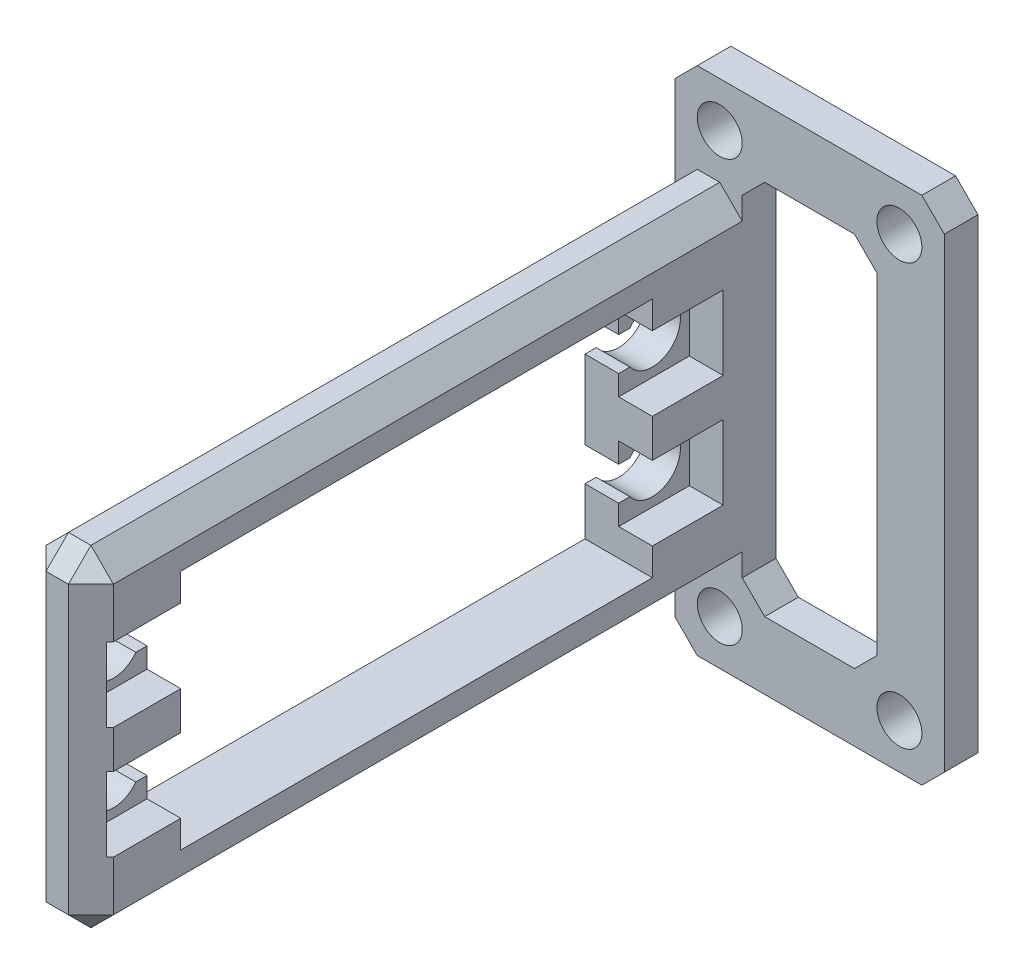
SolidWorks part; units mm, degrees
ref_plane "Front Plane" through (0, 0, 0) normal (0, 0, 1) x (1, 0, 0)
ref_plane "Top Plane" through (0, 0, 0) normal (0, 1, 0) x (1, 0, 0)
ref_plane "Right Plane" through (0, 0, 0) normal (1, 0, 0) x (0, 0, -1)
sketch "Sketch1" plane through (0, 0, 0) normal (1, 0, 0) x (0, 0, -1)
  line L0 (-38.5085, 0.4505) -> (19.4915, 0.4505) construction
  line L1 (-38.5085, 15.2005) -> (19.4915, 15.2005)
  line L2 (-31.5085, 6.9505) -> (-30.5085, 6.9505)
  line L3 (-38.5085, 15.2005) -> (-38.5085, -14.2995)
  line L4 (-38.5085, -14.2995) -> (19.4915, -14.2995)
  line L5 (-30.5085, 3.9505) -> (-31.5085, 3.9505)
  line L6 (11.4915, 3.9505) -> (12.4915, 3.9505)
  line L7 (19.4915, 15.2005) -> (19.4915, -14.2995)
  line L8 (12.4915, 6.9505) -> (11.4915, 6.9505)
  line L9 (11.4915, -3.0495) -> (12.4915, -3.0495)
  line L10 (12.4915, -6.0495) -> (11.4915, -6.0495)
  line L11 (-30.5085, -3.0495) -> (-31.5085, -3.0495)
  line L12 (-28.5085, 10.2005) -> (9.4915, 10.2005) construction
  line L13 (11.4915, -10.2995) -> (-30.5085, -10.2995)
  line L14 (11.4915, 11.2005) -> (-30.5085, 11.2005)
  line L15 (-31.5085, -6.0495) -> (-30.5085, -6.0495)
  line L16 (-30.5085, 3.9505) -> (-30.5085, -3.0495)
  line L17 (-30.5085, -6.0495) -> (-30.5085, -10.2995)
  line L18 (11.4915, -6.0495) -> (11.4915, -10.2995)
  line L19 (11.4915, 3.9505) -> (11.4915, -3.0495)
  line L27 (11.4915, 11.2005) -> (11.4915, 6.9505)
  line L28 (-30.5085, 11.2005) -> (-30.5085, 6.9505)
  line L30 (9.4915, -9.2995) -> (-28.5085, -9.2995) construction
  line L32 (-29.5085, 9.2005) -> (-29.5085, -8.2995) construction
  line L35 (-9.5085, 11.2005) -> (-9.5085, -10.2995) construction
  arc A0 (-31.5085, 6.9505) -> (-31.5085, 3.9505) centre (-33.5085, 5.4505) ccw
  arc A1 (-31.5085, -3.0495) -> (-31.5085, -6.0495) centre (-33.5085, -4.5495) ccw
  arc A2 (12.4915, 3.9505) -> (12.4915, 6.9505) centre (14.4915, 5.4505) ccw
  arc A3 (12.4915, -6.0495) -> (12.4915, -3.0495) centre (14.4915, -4.5495) ccw
  arc A4 (16.3914, 7.0755) -> (16.3914, 3.8255) centre (14.4915, 5.4505) ccw construction
  arc A5 (16.3914, -2.9245) -> (16.3914, -6.1745) centre (14.4915, -4.5495) ccw construction
  arc A6 (-35.4083, -6.1745) -> (-35.4083, -2.9245) centre (-33.5085, -4.5495) ccw construction
  arc A7 (-35.4083, 3.8255) -> (-35.4083, 7.0755) centre (-33.5085, 5.4505) ccw construction
  dimension "D3" = 3
  dimension "D1" = 1
  dimension "D2" = 4
  dimension "D4" = 1
  dimension "D5" = 1
  dimension "D6" = 8
extrude "Boss-Extrude1" add sketch "Sketch1" along normal blind 6
sketch "Sketch2" plane through (6, 0, 0) normal (1, 0, 0) x (0, 0, -1)
  line L0 (-9.5085, 11.2005) -> (-9.5085, -10.2995) construction
  line L1 (-36.8085, 2.1505) -> (-30.2085, 2.1505)
  line L2 (-36.8085, 2.1505) -> (-36.8085, 8.7505)
  line L3 (-36.8085, 8.7505) -> (-30.2085, 8.7505)
  line L4 (-30.2085, 2.1505) -> (-30.2085, 8.7505)
  line L5 (-36.8085, 2.1505) -> (-30.2085, 8.7505) construction
  line L6 (-36.8085, 8.7505) -> (-30.2085, 2.1505) construction
  line L7 (11.4915, 11.2005) -> (-30.5085, 11.2005) construction
  line L8 (11.4915, -10.2995) -> (-30.5085, -10.2995) construction
  line L9 (-38.5085, 0.4505) -> (19.4915, 0.4505) construction
  line L12 (17.7915, 8.7505) -> (11.1915, 2.1505) construction
  line L13 (17.7915, 2.1505) -> (11.1915, 8.7505) construction
  line L14 (11.1915, 2.1505) -> (11.1915, 8.7505)
  line L15 (17.7915, 8.7505) -> (11.1915, 8.7505)
  line L16 (17.7915, 2.1505) -> (17.7915, 8.7505)
  line L17 (17.7915, 2.1505) -> (11.1915, 2.1505)
  line L18 (-38.5085, 15.2005) -> (-38.5085, -14.2995) construction
  line L19 (19.4915, 15.2005) -> (19.4915, -14.2995) construction
  line L20 (-36.8085, -7.8495) -> (-30.2085, -1.2495) construction
  line L21 (-36.8085, -1.2495) -> (-30.2085, -7.8495) construction
  line L22 (-30.2085, -1.2495) -> (-30.2085, -7.8495)
  line L23 (-36.8085, -7.8495) -> (-30.2085, -7.8495)
  line L24 (-36.8085, -1.2495) -> (-36.8085, -7.8495)
  line L25 (-36.8085, -1.2495) -> (-30.2085, -1.2495)
  line L26 (17.7915, -1.2495) -> (11.1915, -7.8495) construction
  line L27 (17.7915, -7.8495) -> (11.1915, -1.2495) construction
  line L28 (17.7915, -1.2495) -> (11.1915, -1.2495)
  line L29 (17.7915, -1.2495) -> (17.7915, -7.8495)
  line L30 (17.7915, -7.8495) -> (11.1915, -7.8495)
  line L31 (11.1915, -1.2495) -> (11.1915, -7.8495)
  point P0 (-33.5085, 5.4505)
  point P1 (-33.5085, 5.4505)
  point P23 (14.4915, 5.4505)
  point P28 (-33.5085, -4.5495)
  point P33 (14.4915, -4.5495)
  dimension "D1" = 6.6
extrude "Cut-Extrude1" cut sketch "Sketch2" against normal blind 3
sketch "Sketch3" plane through (0, 0, -19.4915) normal (0, 0, -1) x (-1, 0, 0)
  line L0 (0, -22.2995) -> (0, 23.2005)
  line L1 (0, 23.2005) -> (-24, 23.2005)
  line L2 (-24, 23.2005) -> (-24, -22.2995)
  line L3 (-24, 0.4505) -> (0, 0.4505) construction
  line L4 (0, 15.2005) -> (0, -14.2995) construction
  line L5 (-4, 19.2005) -> (-4, 23.2005) construction
  line L6 (-4, 19.2005) -> (0, 19.2005) construction
  line L7 (-12, 23.2005) -> (-12, -22.2995) construction
  line L8 (-4, -18.2995) -> (0, -18.2995) construction
  line L9 (-4, -18.2995) -> (-4, -22.2995) construction
  line L10 (0, -22.2995) -> (-24, -22.2995)
  line L12 (-6, -16.2995) -> (-18, -16.2995)
  line L13 (-6, -16.2995) -> (-6, 17.2005)
  line L14 (-6, 17.2005) -> (-18, 17.2005)
  line L15 (-18, -16.2995) -> (-18, 17.2005)
  line L16 (-6, -16.2995) -> (-18, 17.2005) construction
  line L17 (-6, 17.2005) -> (-18, -16.2995) construction
  line L18 (-6, 15.2005) -> (0, 15.2005) construction
  circle A0 centre (-4, 19.2005) radius 2
  circle A1 centre (-20, 19.2005) radius 2
  circle A2 centre (-20, -18.2995) radius 2
  circle A3 centre (-4, -18.2995) radius 2
  point P16 (-12, 0.4505)
  point P24 (-12, 0.4505)
  point P33 (-6, 0.4505)
  dimension "D3" = 4
  dimension "D4" = 4
  dimension "D1" = 24
  dimension "D2" = 8
  dimension "D5" = 6
  dimension "D6" = 6
extrude "Boss-Extrude2" add sketch "Sketch3" along normal blind 3
chamfer "Chamfer5" distance 2 angle 45 4 edges at (6, 17.2005, -20.9915) (18, 17.2005, -20.9915) (18, -16.2995, -20.9915) (6, -16.2995, -20.9915)
chamfer "Chamfer6" distance 2 angle 45 4 edges at (24, -22.2995, -20.9915) (0, -22.2995, -20.9915) (0, 23.2005, -20.9915) (24, 23.2005, -20.9915)
chamfer "Chamfer7" distance 2 angle 45 8 edges at (6, 0.4505, 38.5085) (3, -14.2995, 38.5085) (0, 0.4505, 38.5085) (3, 15.2005, 38.5085)
